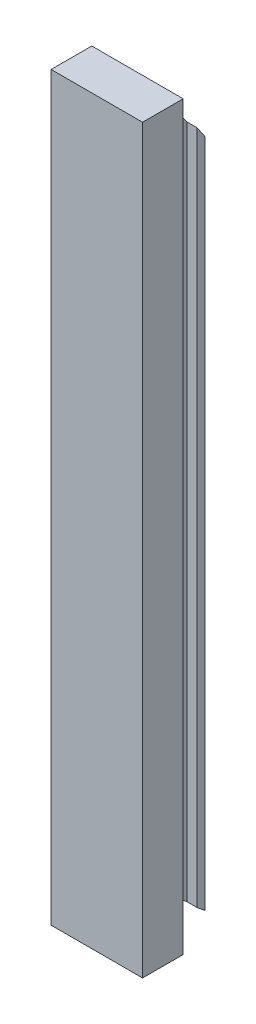
SolidWorks part; units mm, degrees
ref_plane "Front Plane" through (0, 0, 0) normal (0, 0, 1) x (1, 0, 0)
ref_plane "Top Plane" through (0, 0, 0) normal (0, 1, 0) x (1, 0, 0)
ref_plane "Right Plane" through (0, 0, 0) normal (1, 0, 0) x (0, 0, -1)
sketch "Sketch1" plane through (0, 0, 0) normal (0, 0, 1) x (1, 0, 0)
  line L1 (-2, -33) -> (2, -33)
  line L2 (-2, -33) -> (-2, 33)
  line L3 (-2, 33) -> (2, 33)
  line L4 (2, -33) -> (2, 33)
  line L5 (-2, -33) -> (2, 33) construction
  line L6 (-2, 33) -> (2, -33) construction
  point P0 (0, 0)
  dimension "D1" = 4
  dimension "D2" = 66
sketch "Sketch2" plane through (0, 0, 0) normal (1, 0, 0) x (0, 0, -1)
  line L0 (0, 33) -> (-28233.9475, 41298.5329) construction
  line L2 (0, 33) -> (0, -33) construction
  dimension "D1" = 34.38
sketch "Sketch3" plane through (0, 0, 0) normal (1, 0, 0) x (0, 0, -1)
  line L0 (0, -33) -> (38636.6787, -31769.5257) construction
  line L2 (0, -33) -> (0, 33) construction
  dimension "D1" = 50.6
extrude "Boss-Extrude1" add sketch "Sketch1" along direction (0, -0.6347, -0.7727) on the side of the normal blind 1
extrude "Boss-Extrude2" add sketch "Sketch1<2>" along direction (0, 0.8253, 0.5647) on the side of the normal up to surface (0.7727 mm away) up to face at (0, 0.6347, 0.7727)
sketch "Sketch1<2>" plane through (0, 0, 0) normal (0, 0, 1) x (1, 0, 0) same geometry as "Sketch1"
sketch "Sketch4" plane through (0, 0, 0.7727) normal (0, 0, 1) x (1, 0, 0)
  line L0 (-2, -32.3653) -> (2, -32.3653) construction
  line L1 (-1, -32.3653) -> (1, -32.3653)
  line L2 (-1, -32.3653) -> (-1, 34.1294)
  line L3 (-1, 34.1294) -> (1, 34.1294)
  line L4 (1, -32.3653) -> (1, 34.1294)
  line L5 (-1, -32.3653) -> (1, 34.1294) construction
  line L6 (-1, 34.1294) -> (1, -32.3653) construction
  line L7 (-2, 34.1294) -> (2, 34.1294) construction
  line L8 (0, -165029.1317) -> (0, 206360.6647) construction
  point P4 (0, 0.8821)
  point P9 (0, 34.1294)
  dimension "D1" = 2
extrude "Boss-Extrude3" add sketch "Sketch4" along direction (0, -0.6347, -0.7727) on the side of the normal blind 5
extrude "Boss-Extrude4" add sketch "Sketch4<2>" along direction (0, 0.8253, 0.5647) on the side of the normal up to surface (3.8637 mm away) up to face at (0, 4.0557, 4.6364)
sketch "Sketch4<2>" plane through (0, 0, 0.7727) normal (0, 0, 1) x (1, 0, 0) same geometry as "Sketch4"
hole_wizard "Ø3.0mm Dowel Hole1" positions "Sketch6" profile "Sketch8" hole size "Ø3.0" standard "ANSI Metric" end condition through all
sketch "Sketch6" plane through (-1, 0, 0) normal (-1, 0, 0) x (0, 0, 1)
  line L3 (2.7046, -14.1916) -> (4.6364, -14.1916) construction
  line L4 (4.6364, 39.7764) -> (4.6364, -29.1916) construction
  line L6 (2.7046, -14.1916) -> (0.7727, -14.1916) construction
  line L7 (0.7727, 34.1294) -> (0.7727, -32.3653) construction
  point P0 (2.7046, -14.1916)
  point P2 (2.7046, 15.8084)
  dimension "D1" = 15
  dimension "D2" = 45
sketch "Sketch8" plane through (-1, -14.1916, 2.7046) normal (0, 1, 0) x (0, 0, 1)
  line L0 (0, 0) -> (0, 3)
  line L1 (0, 3) -> (1.5, 3)
  line L2 (1.5, 3) -> (1.5, 0)
  line L5 (1.5, 0) -> (0, 0)
  line L11 (0, -6.35) -> (0, 107.95) construction
  dimension "Thru Hole Dia." = 3
  dimension "Thru Hole Depth" = 3
sketch "Sketch9" plane through (0, 0, 4.6364) normal (0, 0, 1) x (1, 0, 0)
  line L0 (-1, -29.1916) -> (1, -29.1916) construction
  line L1 (-4.5, -33.1916) -> (4.5, -33.1916)
  line L2 (-4.5, -33.1916) -> (-4.5, 39.7764)
  line L3 (-4.5, 39.7764) -> (4.5, 39.7764)
  line L4 (4.5, -33.1916) -> (4.5, 39.7764)
  line L5 (-4.5, -33.1916) -> (4.5, 39.7764) construction
  line L6 (-4.5, 39.7764) -> (4.5, -33.1916) construction
  point P4 (0, 3.2924)
  point P5 (0, -33.1916)
  dimension "D1" = 9
  dimension "D2" = 4
extrude "Boss-Extrude6" add sketch "Sketch9" along normal blind 4 contours L3 L4 L1 L2
